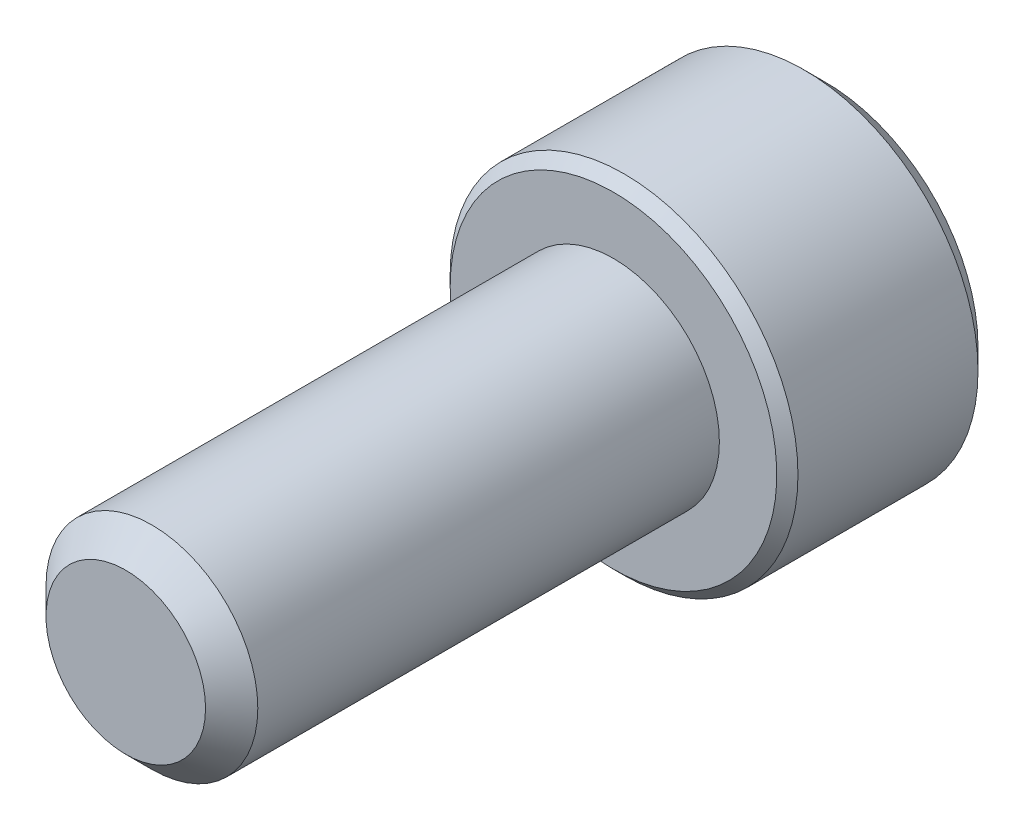
SolidWorks part; units mm, degrees
material "Alloy Steel"
ref_plane "Front Plane" through (0, 0, 0) normal (0, 0, 1) x (1, 0, 0)
ref_plane "Top Plane" through (0, 0, 0) normal (0, 1, 0) x (1, 0, 0)
ref_plane "Right Plane" through (0, 0, 0) normal (1, 0, 0) x (0, 0, -1)
sketch "Sketch1" plane through (0, 0, 0) normal (0, 0, 1) x (1, 0, 0)
  line L0 (0, 2.413) -> (0, -2.413) construction
  circle A0 centre (0, 0) radius 2.413
  dimension "OD" = 4.826
extrude "Extrude1" add sketch "Sketch1" against normal blind 11.1125
sketch "Sketch2" plane through (0, 0, 0) normal (0, 0, 1) x (1, 0, 0)
  circle A0 centre (0, 0) radius 2.413 construction
  circle A1 centre (0, 0) radius 2.413
curve "Helix/Spiral1" pitch 0.7937 height 11.9062 turns 15 parameters "pitch"=0.7937
chamfer "Chamfer3" distance 0.5953 angle 45 1 edges at (2.413, 0, 0)
sketch "Sketch3" plane through (0, 0, 0) normal (1, 0, 0) x (0, 0, -1)
  line L0 (-0.6945, 2.413) -> (-0.3969, 1.8974)
  line L1 (-0.3969, 1.8974) -> (-0.2977, 1.8974)
  line L2 (-0.2977, 1.8974) -> (0, 2.413)
  line L3 (-0.6945, 2.413) -> (0, 2.413)
  line L4 (-0.3473, 2.413) -> (-0.3473, 1.8974) construction
  line L5 (-0.5457, 2.1552) -> (-0.1488, 2.1552) construction
  line L6 (0, 2.413) -> (0, -2.413) construction
  dimension "D1" = 0.0992
  dimension "D2" = 0.3969
  dimension "D3" = 60
sweep "Cut-Sweep1" [suppressed] cut profiles "Sketch3" path "Helix/Spiral1"
sketch "Sketch6" plane through (0, 0, -11.1125) normal (0, 0, -1) x (-1, 0, 0)
  circle A0 centre (0, 0) radius 3.9624
  dimension "head dia" = 7.9248
extrude "Extrude2" add sketch "Sketch6" along normal blind 4.826
sketch "Sketch7" plane through (0, 0, -15.9385) normal (0, 0, -1) x (-1, 0, 0)
  line L1 (0, 2.2914) -> (-1.9844, 1.1457)
  line L2 (-1.9844, 1.1457) -> (-1.9844, -1.1457)
  line L3 (-1.9844, -1.1457) -> (0, -2.2914)
  line L4 (0, -2.2914) -> (1.9844, -1.1457)
  line L5 (1.9844, -1.1457) -> (1.9844, 1.1457)
  line L6 (1.9844, 1.1457) -> (0, 2.2914)
  circle A0 centre (0, 0) radius 1.9844 construction
  dimension "hex dia" = 3.9688
extrude "Cut-Extrude1" cut sketch "Sketch7" against normal blind 2.9766
sketch "Sketch8" plane through (0, 0, -15.9385) normal (0, 0, -1) x (-1, 0, 0)
  circle A0 centre (0, 0) radius 2.2914
extrude "Cut-Extrude2" cut sketch "Sketch8" against normal blind 0.4826 draft 45
chamfer "Chamfer1" distance 0.4826 angle 45 1 edges at (-3.9624, 0, -15.9385)
chamfer "Chamfer2" distance 0.2413 angle 45 1 edges at (-3.9624, 0, -11.1125)
sketch "Sketch9" plane through (0, 0, 0) normal (1, 0, 0) x (0, 0, -1)
  line L0 (0, 2.413) -> (0, -2.413) construction
  line L1 (4.3656, 2.413) -> (4.3656, -2.413) construction
  line L2 (11.1125, 3.9624) -> (11.1125, -3.9624) construction
  line L3 (15.9385, 3.9624) -> (15.9385, -3.9624) construction
  line L4 (15.9385, 0) -> (0, 0) construction
  dimension "D1" = 4.3656
  dimension "D2" = 4.826
  dimension "D3" = 7.9248
  dimension "D4" = 11.1125
equation "\"D3@Helix/Spiral1\" = \"screw length@Extrude1\"+\"pitch@Helix/Spiral1\""
equation "\"D1@Sketch3\" = \"pitch@Helix/Spiral1\"*.125"
equation "\"D2@Sketch3\" = \"pitch@Helix/Spiral1\"*.5"
equation "\"D1@Cut-Extrude1\" = \"hex dia@Sketch7\"*.75"
equation "\"D1@Chamfer1\" = \"head depth@Extrude2\"/10"
equation "\"D1@Sketch9\" = \"pitch@Helix/Spiral1\"*5.5"
equation "\"D1@Chamfer2\" = \"D1@Chamfer1\"/2"
equation "\"D1@Cut-Extrude2\" = \"D1@Chamfer2\"*2"
equation "\"D1@Chamfer3\" = \"pitch@Helix/Spiral1\"*.750"
equation "\"D2@Sketch9\" = \"head depth@Extrude2\""
equation "\"D3@Sketch9\" = \"head dia@Sketch6\""
equation "\"D4@Sketch9\" = \"screw length@Extrude1\""
